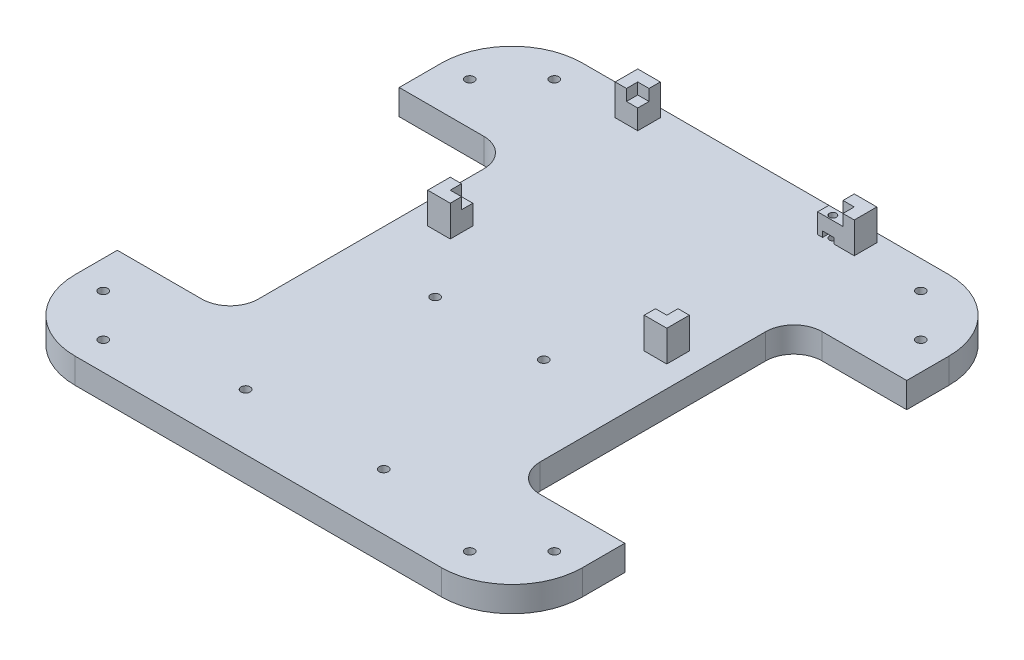
SolidWorks part; units mm, degrees
ref_plane "Front Plane" through (0, 0, 0) normal (0, 0, 1) x (1, 0, 0)
ref_plane "Top Plane" through (0, 0, 0) normal (0, 1, 0) x (1, 0, 0)
ref_plane "Right Plane" through (0, 0, 0) normal (1, 0, 0) x (0, 0, -1)
sketch "Sketch1" plane through (0, 0, 0) normal (0, 1, 0) x (1, 0, 0)
  line L1 (-65, -90) -> (65, -90)
  line L2 (-90, -65) -> (-90, 65)
  line L3 (-65, 90) -> (65, 90)
  line L4 (90, -65) -> (90, 65)
  arc A0 (-90, 65) -> (-65, 90) centre (-65, 65) cw
  arc A1 (65, 90) -> (90, 65) centre (65, 65) cw
  arc A2 (90, -65) -> (65, -90) centre (65, -65) cw
  arc A3 (-65, -90) -> (-90, -65) centre (-65, -65) cw
  point P4 (-90, 0)
  point P6 (0, 90)
  dimension "D3" = 25
  dimension "D1" = 180
  dimension "D2" = 180
extrude "Plate" add sketch "Sketch1" along normal blind 9
sketch "Sketch3" plane through (0, 9, 0) normal (0, 1, 0) x (1, 0, 0)
  line L0 (-65, 90) -> (-65, -90) construction
  line L1 (65, 90) -> (65, -90) construction
  line L2 (-90, 65) -> (90, 65) construction
  line L3 (-90, -65) -> (90, -65) construction
  circle A0 centre (-65, 80) radius 1.6
  circle A1 centre (-80, 65) radius 1.6
  circle A2 centre (80, 65) radius 1.6
  circle A3 centre (80, -65) radius 1.6
  circle A4 centre (65, 80) radius 1.6
  circle A5 centre (65, -80) radius 1.6
  circle A6 centre (-65, -80) radius 1.6
  circle A7 centre (-80, -65) radius 1.6
  dimension "D1" = 3.2
  dimension "D2" = 15
  dimension "D3" = 15
  dimension "D4" = 15
  dimension "D5" = 15
  dimension "D6" = 15
  dimension "D7" = 15
  dimension "D8" = 15
  dimension "D9" = 15
extrude "Hex Holes" cut sketch "Sketch3" against normal through all
sketch "Sketch4" plane through (0, 9, 0) normal (0, 1, 0) x (1, 0, 0)
  line L0 (-90, -65) -> (-90, 65) construction
  line L1 (-65, -90) -> (65, -90) construction
  circle A0 centre (-24.5, -70) radius 1.6
  circle A1 centre (24.5, -70) radius 1.6
  circle A2 centre (-19.25, -8) radius 1.6
  circle A3 centre (19.25, -8) radius 1.6
  dimension "D1" = 3.2
  dimension "D2" = 62
  dimension "D3" = 49
  dimension "D4" = 5.25
  dimension "D5" = 38.5
  dimension "D6" = 65.5
  dimension "D7" = 20
extrude "Arduino Holes" cut sketch "Sketch4" against normal through all
sketch "Sketch5" plane through (0, 9, 0) normal (0, 1, 0) x (1, 0, 0)
  line L0 (-90, -65) -> (-90, 65) construction
  line L1 (-90, -50) -> (-50, -50)
  line L2 (-90, -50) -> (-90, 50)
  line L3 (-90, 50) -> (-50, 50)
  line L4 (-50, -50) -> (-50, 50)
  line L5 (90, -65) -> (90, 65) construction
  line L6 (90, -50) -> (50, -50)
  line L7 (90, -50) -> (90, 50)
  line L8 (90, 50) -> (50, 50)
  line L9 (50, -50) -> (50, 50)
  line L10 (-90, 0) -> (90, 0) construction
  point P14 (-90, 0)
  point P15 (90, 0)
  dimension "D1" = 100
  dimension "D3" = 40
extrude "Cut-Extrude1" cut sketch "Sketch5" against normal through all
fillet "Fillet1" radius 10 4 edges at (50, 4.5, -50) (50, 4.5, 50) (-50, 4.5, -50) (-50, 4.5, 50)
sketch "Sketch6" plane through (0, 9, 0) normal (0, 1, 0) x (1, 0, 0)
  line L0 (-65, 90) -> (65, 90) construction
  line L1 (-38.4, 16.5) -> (38.4, 16.5) construction
  line L2 (-38.4, 16.5) -> (-38.4, 83) construction
  line L3 (-38.4, 83) -> (38.4, 83) construction
  line L4 (38.4, 16.5) -> (38.4, 83) construction
  line L5 (34.4, 83) -> (38.4, 83)
  line L6 (38.4, 83) -> (38.4, 79)
  line L7 (38.4, 79) -> (42.4, 79)
  line L8 (42.4, 79) -> (42.4, 87)
  line L9 (42.4, 87) -> (34.4, 87)
  line L10 (34.4, 87) -> (34.4, 83)
  line L11 (38.4, 20.5) -> (38.4, 16.5)
  line L12 (38.4, 16.5) -> (34.4, 16.5)
  line L13 (34.4, 16.5) -> (34.4, 12.5)
  line L14 (34.4, 12.5) -> (42.4, 12.5)
  line L15 (42.4, 12.5) -> (42.4, 20.5)
  line L16 (42.4, 20.5) -> (38.4, 20.5)
  line L17 (-38.4, 16.5) -> (-34.4, 16.5)
  line L18 (-34.4, 16.5) -> (-34.4, 12.5)
  line L19 (-34.4, 12.5) -> (-42.4, 12.5)
  line L20 (-42.4, 12.5) -> (-42.4, 20.5)
  line L21 (-42.4, 20.5) -> (-38.4, 20.5)
  line L22 (-38.4, 20.5) -> (-38.4, 16.5)
  line L23 (-38.4, 83) -> (-34.4, 83)
  line L24 (-34.4, 83) -> (-34.4, 87)
  line L25 (-34.4, 87) -> (-42.4, 87)
  line L26 (-42.4, 87) -> (-42.4, 79)
  line L27 (-42.4, 79) -> (-38.4, 79)
  line L28 (-38.4, 79) -> (-38.4, 83)
  point P6 (0, 90)
  point P7 (0, 83)
  dimension "D1" = 66.5
  dimension "D2" = 76.8
  dimension "D3" = 7
  dimension "D4" = 4
extrude "Boss-Extrude1" add sketch "Sketch6" along normal blind 11
sketch "Sketch7" plane through (0, 9, 0) normal (0, 1, 0) x (1, 0, 0)
  line L1 (-38.4, 16.5) -> (-34.4, 16.5)
  line L2 (-38.4, 16.5) -> (-38.4, 20.5)
  line L3 (-38.4, 20.5) -> (-34.4, 20.5)
  line L4 (-34.4, 16.5) -> (-34.4, 20.5)
  line L5 (38.4, 16.5) -> (34.4, 16.5)
  line L6 (38.4, 16.5) -> (38.4, 20.5)
  line L7 (38.4, 20.5) -> (34.4, 20.5)
  line L8 (34.4, 16.5) -> (34.4, 20.5)
  line L9 (-38.4, 83) -> (-34.4, 83)
  line L10 (-38.4, 83) -> (-38.4, 79)
  line L11 (-38.4, 79) -> (-34.4, 79)
  line L12 (-34.4, 83) -> (-34.4, 79)
  line L13 (38.4, 83) -> (29.4, 83)
  line L14 (38.4, 83) -> (38.4, 79)
  line L15 (38.4, 79) -> (29.4, 79)
  line L16 (29.4, 83) -> (29.4, 79)
  dimension "D1" = 4
  dimension "D2" = 4
  dimension "D3" = 9
extrude "Boss-Extrude2" add sketch "Sketch7" along normal blind 7
sketch "Sketch8" plane through (0, 16, 0) normal (0, 1, 0) x (1, 0, 0)
  line L0 (38.4, 83) -> (34.4, 83) construction
  line L1 (38.4, 79) -> (38.4, 83) construction
  line L2 (29.4, 83) -> (29.4, 79) construction
  circle A0 centre (33.15, 80.65) radius 1.25
  point P4 (0, 0)
  point P6 (36.4895, 80.0004)
  dimension "D1" = 2.5
  dimension "D2" = 2.35
  dimension "D3" = 5.25
extrude "Cut-Extrude2" cut sketch "Sketch8" against normal through all
sketch "Sketch9" plane through (0, 0, -79) normal (0, 0, 1) x (1, 0, 0)
  line L0 (29.4, 9) -> (42.4, 9) construction
  line L1 (31.15, 11) -> (35.15, 11)
  line L2 (31.15, 11) -> (31.15, 9)
  line L3 (31.15, 9) -> (35.15, 9)
  line L4 (35.15, 11) -> (35.15, 9)
  line L6 (29.4, 16) -> (29.4, 9) construction
  point P6 (33.15, 11)
  dimension "D1" = 4
  dimension "D2" = 2
  dimension "D3" = 3.75
extrude "Cut-Extrude3" cut sketch "Sketch9" against normal through all
